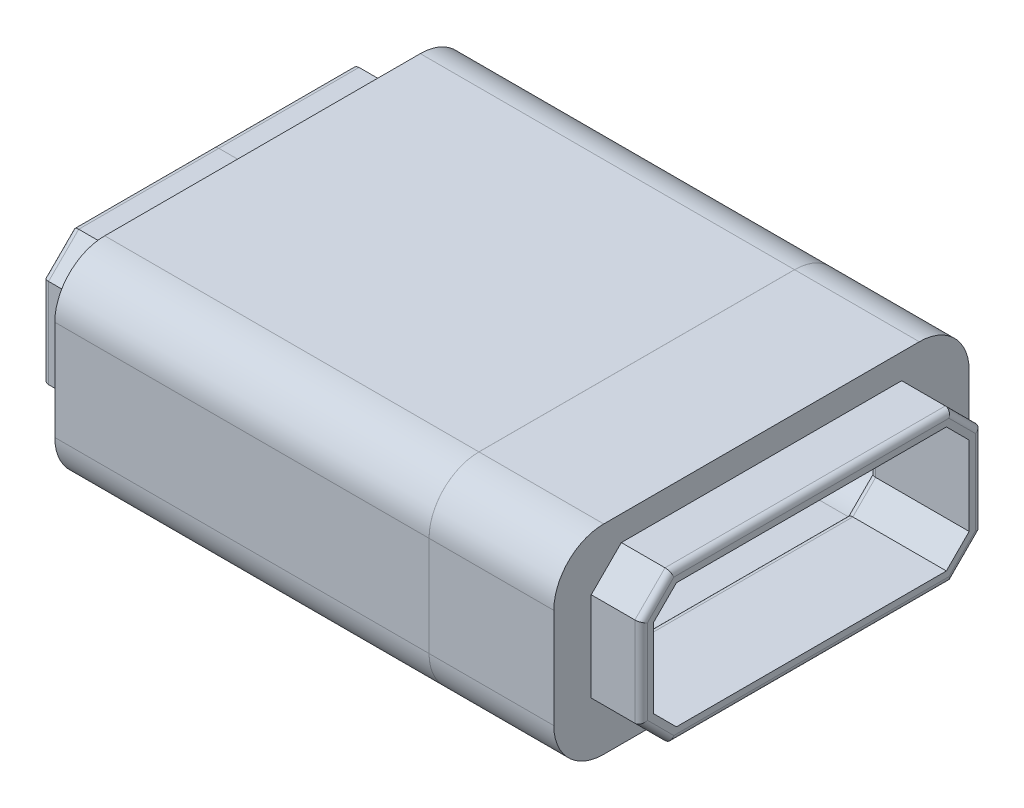
SolidWorks part; units mm, degrees
ref_plane "Front" through (0, 0, 0) normal (0, 0, 1) x (1, 0, 0)
ref_plane "Top" through (0, 0, 0) normal (0, 1, 0) x (1, 0, 0)
ref_plane "Right" through (0, 0, 0) normal (1, 0, 0) x (0, 0, -1)
sketch "Sketch2path" plane through (0, 0, 0) normal (0, 0, 1) x (1, 0, 0)
  line L0 (30.0026, 0) -> (40.0026, -0.0017)
  line L1 (0, 0) -> (30, 0)
  arc A1 (30, 0) -> (30.0026, 0) centre (30, -15) cw
  point P5 (30.0013, 0)
  dimension "D1" = 30
  dimension "D2" = 0.01
  dimension "D4" = 15
  dimension "D3" = 10
sketch "Sketch3" plane through (0, 0, 0) normal (1, 0, 0) x (0, 0, -1)
  line L0 (-16.65, -4) -> (-16.65, 4)
  line L1 (-12.65, 8) -> (12.65, 8)
  line L2 (16.65, 4) -> (16.65, -4)
  line L3 (12.65, -8) -> (-12.65, -8)
  line L4 (-15.65, -4) -> (-15.65, 4)
  line L5 (12.65, -7) -> (-12.65, -7)
  line L6 (0, 91.8161) -> (0, -91.8161) construction
  line L12 (15.65, 4) -> (15.65, -4)
  line L13 (-12.65, 7) -> (12.65, 7)
  arc A0 (-12.65, 8) -> (-16.65, 4) centre (-12.65, 4) ccw
  arc A1 (16.65, 4) -> (12.65, 8) centre (12.65, 4) ccw
  arc A2 (12.65, -8) -> (16.65, -4) centre (12.65, -4) ccw
  arc A3 (-16.65, -4) -> (-12.65, -8) centre (-12.65, -4) ccw
  arc A4 (-12.65, 7) -> (-15.65, 4) centre (-12.65, 4) ccw
  arc A5 (-15.65, -4) -> (-12.65, -7) centre (-12.65, -4) ccw
  arc A10 (12.65, -7) -> (15.65, -4) centre (12.65, -4) ccw
  arc A11 (15.65, 4) -> (12.65, 7) centre (12.65, 4) ccw
  dimension "D1" = 4
  dimension "D2" = 3
  dimension "D3" = 15.65
  dimension "D4" = 15.65
  dimension "D5" = 7
  dimension "D6" = 7
sweep "Sweep1" add profiles "Sketch3" path "Sketch2path"
ref_point "Point1S1"
ref_point "Point2S3"
ref_axis "os podluzna S1" through (0, 0, 0) along (-1, 0, 0)
ref_axis "os podluzna S3" through (40.0026, -0.0017, 0) along (1, -0.0002, 0)
sketch "Sketch24" plane through (0, 0, 0) normal (0, 0, 1) x (1, 0, 0)
  line L0 (0, -8) -> (0, -7)
  line L1 (0, 7) -> (0, 8)
  line L2 (30, 8) -> (0, 8) construction
  line L3 (0, -8) -> (0, -7)
  line L4 (0, 8) -> (4, 8)
  line L6 (4, 8) -> (4, 5)
  line L7 (4, 5) -> (-4, 5)
  line L8 (-4, 5) -> (-4, 6)
  line L9 (-4, 6) -> (0, 6)
  line L10 (0, 7) -> (0, 4) construction
  line L11 (0, 6) -> (0, 8)
  dimension "D1" = 4
  dimension "D2" = 8
  dimension "D3" = 3
  dimension "D4" = 1
sketch "Sketch25" plane through (0, 0, 0) normal (-1, 0, 0) x (0, 0, 1)
  line L0 (12.65, 7) -> (-12.65, 7) construction
  line L2 (-12.65, -7) -> (12.65, -7) construction
  line L4 (11.65, 7) -> (-11.65, 7)
  line L5 (14.65, -4) -> (14.65, 4)
  line L6 (-11.65, -7) -> (11.65, -7)
  line L8 (-14.65, 4) -> (-14.65, -4)
  arc A4 (11.65, -7) -> (14.65, -4) centre (11.65, -4) ccw
  arc A5 (14.65, 4) -> (11.65, 7) centre (11.65, 4) ccw
  arc A8 (-11.65, 7) -> (-14.65, 4) centre (-11.65, 4) ccw
  arc A9 (-14.65, -4) -> (-11.65, -7) centre (-11.65, -4) ccw
sweep "Sweep3" add profiles "Sketch24" path "Sketch25"
sketch "Sketch26" plane through (-4, 0, 0) normal (-1, 0, 0) x (0, 0, 1)
  line L8 (-13.65, 3.5858) -> (-11.2358, 6)
  line L9 (-11.65, 6) -> (-11.2358, 6)
  line L10 (-13.65, 3.5858) -> (-13.65, 4)
  arc A3 (-11.65, 6) -> (-13.65, 4) centre (-11.65, 4) ccw
extrude "Cut-Extrude6" cut sketch "Sketch26" against normal up to surface (4 mm away)
sketch "Sketch27" plane through (-4, 0, 0) normal (-1, 0, 0) x (0, 0, 1)
  line L4 (-12.9429, 2.8787) -> (-10.5287, 5.2929)
  line L5 (-13.65, 3.5858) -> (-11.2358, 6)
  line L6 (-11.2358, 6) -> (-10.5287, 5.2929)
  line L7 (-13.65, 3.5858) -> (-12.9429, 2.8787)
  line M4 (-11.65, 5) -> (0, 5)
  line M10 (-11.65, 5.5858) -> (-11.65, 5)
  line M11 (-11.2358, 6) -> (-11.65, 5.5858)
extrude "Boss-Extrude11" add sketch "Sketch27" against normal blind 4 contours L5 L7 L4 M4 M10 | L6 L4 M11 M10 M4 region at (-4, 4.1744, -12.343) region at (-4, 5.3925, -11.1767)
mirror "Mirror1" about plane through (0, 0, 0) normal (0, 0, 1) of "Boss-Extrude11", "Cut-Extrude6"
mirror "Mirror2" about plane through (0, 0, 0) normal (0, 1, 0) of "Mirror1"
fillet "Fillet6" radius 0.5 10 edges at (-4, 4.7929, -12.4429) (-4, 0, 13.65) (-4, 4.7929, 12.4429) (-4, -4.7929, 12.4429) (-4, -6, 0) (-4, -4.7929, -12.4429) (-4, 0, -13.65)
sketch "Sketch36" plane through (40.0026, -0.007, 0) normal (1, -0.0002, 0) x (0, 0, -1)
  line L0 (-15.65, 4.0052) -> (-15.65, -3.9948) construction
  line L1 (12.65, 7.0052) -> (-12.65, 7.0052) construction
  line L2 (15.65, -3.9948) -> (15.65, 4.0052) construction
  line L3 (-12.65, -6.9948) -> (12.65, -6.9948) construction
  line L4 (-15.65, 4.0052) -> (-15.65, -3.9948)
  line L5 (12.65, 7.0052) -> (-12.65, 7.0052)
  line L6 (15.65, -3.9948) -> (15.65, 4.0052)
  line L7 (-12.65, -6.9948) -> (12.65, -6.9948)
  line L8 (-12.65, -4.9948) -> (12.65, -4.9948) construction
  line L9 (-11.65, -4.9948) -> (11.65, -4.9948)
  line L11 (11.65, 5.0052) -> (-11.65, 5.0052)
  line L12 (-12.65, 4.0052) -> (-12.65, -3.9948)
  line L13 (12.65, 5.0052) -> (-12.65, 5.0052) construction
  line L14 (-13.65, 4.0052) -> (-13.65, -3.9948) construction
  line L16 (12.65, -3.9948) -> (12.65, 4.0052)
  line L17 (13.65, -3.9948) -> (13.65, 4.0052) construction
  arc A0 (-12.65, 7.0052) -> (-15.65, 4.0052) centre (-12.65, 4.0052) ccw construction
  arc A1 (15.65, 4.0052) -> (12.65, 7.0052) centre (12.65, 4.0052) ccw construction
  arc A2 (12.65, -6.9948) -> (15.65, -3.9948) centre (12.65, -3.9948) ccw construction
  arc A3 (-15.65, -3.9948) -> (-12.65, -6.9948) centre (-12.65, -3.9948) ccw construction
  arc A4 (-12.65, 7.0052) -> (-15.65, 4.0052) centre (-12.65, 4.0052) ccw
  arc A5 (15.65, 4.0052) -> (12.65, 7.0052) centre (12.65, 4.0052) ccw
  arc A6 (12.65, -6.9948) -> (15.65, -3.9948) centre (12.65, -3.9948) ccw
  arc A7 (-15.65, -3.9948) -> (-12.65, -6.9948) centre (-12.65, -3.9948) ccw
  arc A8 (11.65, -4.9948) -> (12.65, -3.9948) centre (11.65, -3.9948) ccw
  arc A9 (12.65, 4.0052) -> (11.65, 5.0052) centre (11.65, 4.0052) ccw
  arc A12 (-12.65, -3.9948) -> (-11.65, -4.9948) centre (-11.65, -3.9948) ccw
  arc A13 (-11.65, 5.0052) -> (-12.65, 4.0052) centre (-11.65, 4.0052) ccw
  arc A14 (-12.65, 5.0052) -> (-13.65, 4.0052) centre (-12.65, 4.0052) ccw construction
  arc A15 (-13.65, -3.9948) -> (-12.65, -4.9948) centre (-12.65, -3.9948) ccw construction
  arc A17 (12.65, -4.9948) -> (13.65, -3.9948) centre (12.65, -3.9948) ccw construction
  arc A18 (13.65, 4.0052) -> (12.65, 5.0052) centre (12.65, 4.0052) ccw construction
  dimension "D1" = 2
extrude "Boss-Extrude14" add sketch "Sketch36" against normal blind 4
sketch "Sketch37" plane through (40.0026, -0.007, 0) normal (1, -0.0002, 0) x (0, 0, -1)
  line L4 (12.65, -3.9948) -> (12.65, 4.0052) construction
  line L5 (-11.65, -4.9948) -> (11.65, -4.9948) construction
  line L6 (-12.65, 4.0052) -> (-12.65, -3.9948) construction
  line L7 (11.65, 5.0052) -> (-11.65, 5.0052) construction
  line L8 (12.65, -3.9948) -> (12.65, 4.0052)
  line L9 (-11.65, -4.9948) -> (11.65, -4.9948)
  line L10 (-12.65, 4.0052) -> (-12.65, -3.9948)
  line L11 (11.65, 5.0052) -> (-11.65, 5.0052)
  line L12 (11.65, 6.0052) -> (-11.65, 6.0052)
  line L13 (-13.65, 4.0052) -> (-13.65, -3.9948)
  line L14 (-11.65, -5.9948) -> (11.65, -5.9948)
  line L15 (13.65, -3.9948) -> (13.65, 4.0052)
  arc A4 (11.65, -4.9948) -> (12.65, -3.9948) centre (11.65, -3.9948) ccw construction
  arc A5 (-12.65, -3.9948) -> (-11.65, -4.9948) centre (-11.65, -3.9948) ccw construction
  arc A6 (-11.65, 5.0052) -> (-12.65, 4.0052) centre (-11.65, 4.0052) ccw construction
  arc A7 (12.65, 4.0052) -> (11.65, 5.0052) centre (11.65, 4.0052) ccw construction
  arc A8 (11.65, -4.9948) -> (12.65, -3.9948) centre (11.65, -3.9948) ccw
  arc A9 (-12.65, -3.9948) -> (-11.65, -4.9948) centre (-11.65, -3.9948) ccw
  arc A10 (-11.65, 5.0052) -> (-12.65, 4.0052) centre (-11.65, 4.0052) ccw
  arc A11 (12.65, 4.0052) -> (11.65, 5.0052) centre (11.65, 4.0052) ccw
  arc A12 (-11.65, 6.0052) -> (-13.65, 4.0052) centre (-11.65, 4.0052) ccw
  arc A13 (-13.65, -3.9948) -> (-11.65, -5.9948) centre (-11.65, -3.9948) ccw
  arc A14 (11.65, -5.9948) -> (13.65, -3.9948) centre (11.65, -3.9948) ccw
  arc A15 (13.65, 4.0052) -> (11.65, 6.0052) centre (11.65, 4.0052) ccw
  dimension "D1" = 1
extrude "Boss-Extrude15" add sketch "Sketch37" along normal blind 4
sketch "Sketch38" plane through (44.0026, -0.0077, 0) normal (1, -0.0002, 0) x (0, 0, -1)
  line L3 (-13.9429, 6.2981) -> (-11.9429, 6.2981)
  line L4 (-13.9429, 3.2981) -> (-10.9429, 6.2981)
  line L6 (-13.9429, 3.2981) -> (-13.9429, 6.2981)
  line L7 (-13.9429, 6.2981) -> (-10.9429, 6.2981)
  line M22 (11.65, 6.0052) -> (-11.65, 6.0052)
  arc M23 (-11.65, 6.0052) -> (-13.65, 4.0052) centre (-11.65, 4.0052) ccw
  line M24 (-13.65, 4.0052) -> (-13.65, -3.9948)
extrude "Cut-Extrude9" cut sketch "Sketch38" against normal blind 4 contours L4 M24 M22 M23 | L7 L3 L6 L4 M24 M23 M22 region at (44.0036, 5.4983, 13.1507) region at (44.0035, 5.0433, 12.6958)
sketch "Sketch39" plane through (44.0026, -0.0077, 0) normal (1, -0.0002, 0) x (0, 0, -1)
  line L5 (-12.9429, 2.8839) -> (-10.5287, 5.2981)
  line L6 (-10.5287, 5.2981) -> (-11.2358, 6.0052)
  line L7 (-13.65, 3.591) -> (-11.2358, 6.0052)
  line L8 (-13.65, 3.591) -> (-12.9429, 2.8839)
extrude "Boss-Extrude16" add sketch "Sketch39" against normal blind 8
mirror "Mirror7" about plane through (0, 0, 0) normal (0, 0, 1) of "Cut-Extrude9", "Boss-Extrude16"
ref_plane "Plane1" through (0, 0.0052, 0) normal (0.0002, 1, 0) x (1, -0.0002, 0)
mirror "Mirror9" about plane through (0, 0.0052, 0) normal (0.0002, 1, 0) of "Mirror7"
fillet "Fillet7" radius 0.5 24 edges at (36.0026, -0.001, 15.65) (36.0015, -6.1224, 14.7713) (36.0014, -7.001, 0) (36.0015, -6.1224, -14.7713) (36.0026, -0.001, -15.65) (36.0037, 6.1203, -14.7713) (36.0038, 6.999, 0) (36.0037, 6.1203, 14.7713) (36.0035, 4.999, 0) (36.0017, -5.001, 0) (36.0026, -0.001, 12.65) (36.0026, -0.001, -12.65) (36.0033, 4.0847, 11.7358) (36.0033, 4.0847, -11.7358) (36.0019, -4.0868, -11.7358) (36.0019, -4.0868, 11.7358) (44.0035, 4.7904, -12.4429) (44.0026, -0.0024, -13.65) (44.0018, -4.7953, -12.4429) (44.0016, -6.0024, 0) (44.0018, -4.7953, 12.4429) (44.0026, -0.0024, 13.65) (44.0037, 5.9976, 0) (44.0035, 4.7904, 12.4429)
ref_plane "Plane4 polowki" [suppressed] through (0, 0, 0) normal (0, 0, 1) x (1, 0, 0)
other "SurfaceCut1prawa" [suppressed]
other "SurfaceCut3lewa" [suppressed]
